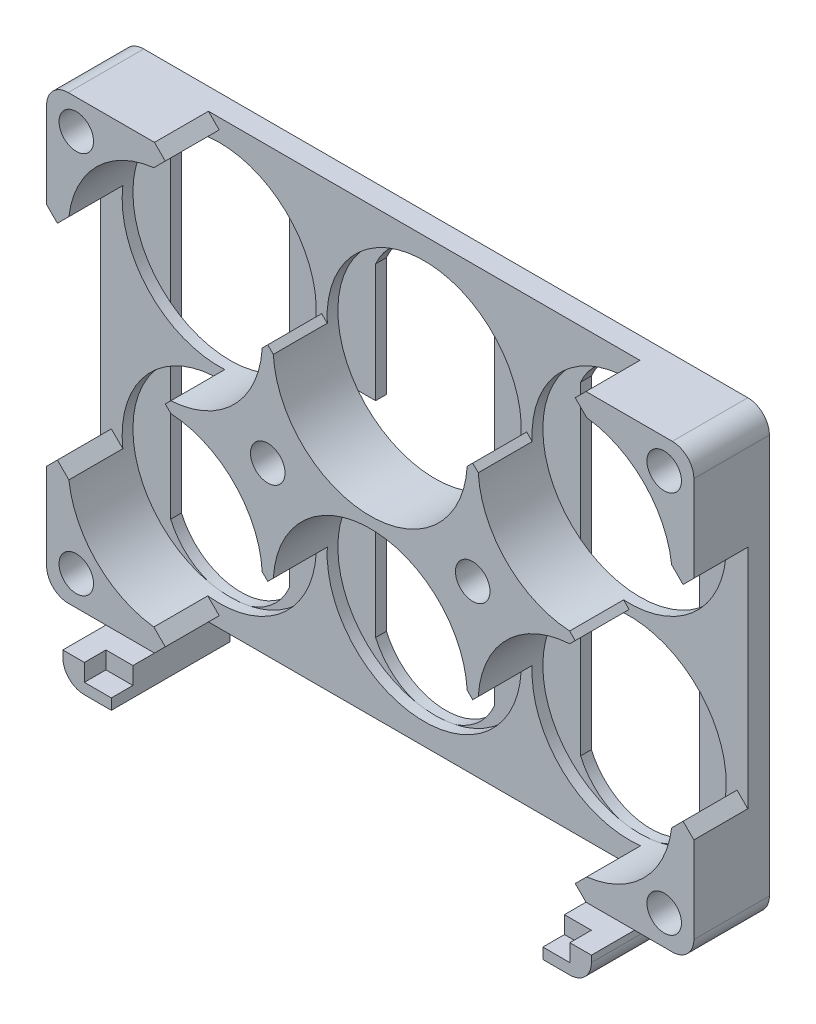
SolidWorks part; units mm, degrees
ref_plane "Płaszczyzna przednia" through (0, 0, 0) normal (0, 0, 1) x (1, 0, 0)
ref_plane "Płaszczyzna górna" through (0, 0, 0) normal (0, 1, 0) x (1, 0, 0)
ref_plane "Płaszczyzna prawa" through (0, 0, 0) normal (1, 0, 0) x (0, 0, -1)
sketch "Sketch1" plane through (0, 0, 0) normal (0, 0, 1) x (1, 0, 0)
  line L1 (0, 0) -> (-60, 0)
  line L2 (0, 0) -> (0, 41)
  line L3 (0, 41) -> (-60, 41)
  line L4 (-60, 0) -> (-60, 41)
  line L5 (0, 0) -> (-60, 41) construction
  line L6 (0, 41) -> (-60, 0) construction
  point P4 (-30, 20.5)
  dimension "D1" = 60
  dimension "D2" = 41
extrude "Boss-Extrude1" add sketch "Sketch1" along normal blind 2
sketch "Sketch2" plane through (0, 0, 2) normal (0, 0, 1) x (1, 0, 0)
  line L0 (-60, 41) -> (-60, 0) construction
  line L1 (-60, 0) -> (0, 0) construction
  circle A0 centre (-49, 11) radius 9
  circle A1 centre (-30, 11) radius 9
  circle A2 centre (-11, 11) radius 9
  circle A3 centre (-30, 30) radius 9
  circle A4 centre (-11, 30) radius 9
  circle A5 centre (-49, 30) radius 9
  dimension "D1" = 18
  dimension "D2" = 11
  dimension "D3" = 11
  dimension "D4" = 3
  dimension "D5" = 2
extrude "Cut-Extrude1" cut sketch "Sketch2" against normal blind 1
sketch "Sketch3" plane through (0, 0, 0) normal (0, 0, -1) x (-1, 0, 0)
  line L0 (60, 41) -> (60, 0) construction
  line L2 (54.5, 35.4979) -> (54.5, 5.4979)
  line L4 (43.5, 35.4979) -> (43.5, 5.4979)
  line L5 (54.5, 35.4979) -> (43.5, 5.4979) construction
  line L6 (54.5, 5.4979) -> (43.5, 35.4979) construction
  line L7 (0, 41) -> (60, 41) construction
  line L8 (60, 0) -> (0, 0) construction
  line L9 (35.5, 35.4979) -> (35.5, 5.4979)
  line L10 (24.5, 35.4979) -> (24.5, 5.4979)
  line L11 (16.5, 35.4979) -> (16.5, 5.4979)
  line L12 (5.5, 35.4979) -> (5.5, 5.4979)
  line L13 (0, 0) -> (0, 41) construction
  arc A0 (43.5, 35.4979) -> (54.5, 35.4979) centre (49, 33.1) cw
  arc A1 (54.5, 5.4979) -> (43.5, 5.4979) centre (49, 7.8958) cw
  arc A2 (35.5, 5.4979) -> (24.5, 5.4979) centre (30, 7.8958) cw
  arc A3 (24.5, 35.4979) -> (35.5, 35.4979) centre (30, 33.1) cw
  arc A4 (16.5, 5.4979) -> (5.5, 5.4979) centre (11, 7.8958) cw
  arc A5 (5.5, 35.4979) -> (16.5, 35.4979) centre (11, 33.1) cw
  point P4 (49, 20.4979)
  dimension "D4" = 6
  dimension "D5" = 6
  dimension "D6" = 7.9
  dimension "D1" = 11
  dimension "D2" = 30
  dimension "D3" = 5.5
  dimension "D7" = 30
  dimension "D8" = 7.8958
  dimension "D10" = 5.5
  dimension "D9" = 3
extrude "Cut-Extrude2" cut sketch "Sketch3" against normal blind 1
sketch "Sketch4" plane through (0, 0, 0) normal (0, 0, -1) x (-1, 0, 0)
  line L0 (43.5, 35.4979) -> (43.5, 5.4979) construction
  line L1 (43.5, 24.5061) -> (35.5, 24.5061)
  line L2 (43.5, 24.5061) -> (43.5, 16.5061)
  line L3 (43.5, 16.5061) -> (35.5, 16.5061)
  line L4 (35.5, 24.5061) -> (35.5, 16.5061)
  line L5 (43.5, 24.5061) -> (35.5, 16.5061) construction
  line L6 (43.5, 16.5061) -> (35.5, 24.5061) construction
  line L7 (35.5, 5.4979) -> (35.5, 35.4979) construction
  point P4 (39.5, 20.5061)
  dimension "D1" = 8
  dimension "D2" = 1.63
extrude "Cut-Extrude3" cut sketch "Sketch4" against normal blind 1
sketch "Sketch5" plane through (0, 0, 2) normal (0, 0, 1) x (1, 0, 0)
  line L0 (-49, 20) -> (-49, 21)
  line L1 (-40, 30) -> (-39, 30)
  line L2 (-40, 11) -> (-39, 11)
  line L3 (-21, 11) -> (-20, 11)
  line L4 (-11, 20) -> (-11, 21)
  line L5 (-20, 30) -> (-21, 30)
  line L6 (-2, 30) -> (0, 30)
  line L7 (0, 0) -> (0, 41) construction
  line L8 (0, 30) -> (0, 41)
  line L9 (0, 41) -> (-11, 41)
  line L10 (0, 41) -> (-60, 41) construction
  line L11 (-11, 41) -> (-11, 39)
  line L12 (-2, 11) -> (0, 11)
  line L13 (0, 11) -> (0, 0)
  line L14 (0, 0) -> (-11, 0)
  line L15 (-60, 0) -> (0, 0) construction
  line L16 (-11, 0) -> (-11, 2)
  line L17 (-49, 2) -> (-49, 0)
  line L18 (-49, 0) -> (-60, 0)
  line L19 (-60, 0) -> (-60, 11)
  line L20 (-60, 41) -> (-60, 0) construction
  line L21 (-60, 11) -> (-58, 11)
  line L22 (-58, 30) -> (-60, 30)
  line L23 (-60, 30) -> (-60, 41)
  line L24 (-60, 41) -> (-49, 41)
  line L25 (-49, 41) -> (-49, 39)
  arc A0 (-49, 20) -> (-40, 11) centre (-49, 11) cw
  circle A1 centre (-49, 11) radius 9 construction
  arc A2 (-49, 21) -> (-40, 30) centre (-49, 30) ccw
  circle A3 centre (-49, 30) radius 9 construction
  arc A4 (-39, 30) -> (-30, 21) centre (-30, 30) ccw
  circle A5 centre (-30, 30) radius 9 construction
  arc A6 (-30, 20) -> (-39, 11) centre (-30, 11) ccw
  circle A7 centre (-30, 11) radius 9 construction
  arc A8 (-30, 20) -> (-21, 11) centre (-30, 11) cw
  arc A9 (-30, 21) -> (-21, 30) centre (-30, 30) ccw
  arc A10 (-20, 30) -> (-11, 21) centre (-11, 30) ccw
  circle A11 centre (-11, 30) radius 9 construction
  arc A12 (-11, 20) -> (-20, 11) centre (-11, 11) ccw
  circle A13 centre (-11, 11) radius 9 construction
  arc A14 (-11, 2) -> (-2, 11) centre (-11, 11) ccw
  arc A15 (-11, 39) -> (-2, 30) centre (-11, 30) cw
  arc A16 (-58, 30) -> (-49, 39) centre (-49, 30) cw
  arc A17 (-58, 11) -> (-49, 2) centre (-49, 11) ccw
extrude "Boss-Extrude2" add sketch "Sketch5" along normal blind 5
sketch "Sketch6" plane through (0, 0, 7) normal (0, 0, 1) x (1, 0, 0)
  line L0 (-21, 11) -> (-20, 11) construction
  line L1 (-20, 30) -> (-21, 30) construction
  line L2 (-11, 20) -> (-11, 21) construction
  line L3 (-49, 21) -> (-49, 20) construction
  line L4 (-39, 30) -> (-40, 30) construction
  line L5 (-60, 41) -> (-60, 30) construction
  line L6 (-49, 41) -> (-60, 41) construction
  line L7 (-60, 0) -> (-49, 0) construction
  line L8 (-60, 11) -> (-60, 0) construction
  line L9 (0, 0) -> (0, 11) construction
  line L10 (-11, 0) -> (0, 0) construction
  line L11 (0, 30) -> (0, 41) construction
  line L12 (0, 41) -> (-11, 41) construction
  circle A0 centre (-39.5, 20.5) radius 1.6
  circle A1 centre (-20.5, 20.5) radius 1.6
  circle A2 centre (-2.75, 2.75) radius 1.6
  circle A3 centre (-2.75, 38.25) radius 1.6
  circle A4 centre (-57.25, 38.25) radius 1.6
  circle A5 centre (-57.25, 2.75) radius 1.6
  dimension "D1" = 3.2
  dimension "D2" = 3.2
  dimension "D3" = 3.2
  dimension "D4" = 3.2
  dimension "D5" = 3.2
  dimension "D6" = 3.2
  dimension "D7" = 9.5
  dimension "D8" = 9.5
  dimension "D9" = 9.5
  dimension "D10" = 9.5
  dimension "D11" = 9.5
  dimension "D12" = 2.75
  dimension "D13" = 2.75
  dimension "D14" = 2.75
  dimension "D15" = 2.75
  dimension "D16" = 2.75
  dimension "D17" = 2.75
  dimension "D18" = 2.75
  dimension "D19" = 2.75
extrude "Cut-Extrude4" cut sketch "Sketch6" against normal through all
chamfer "Chamfer1" distance 1 angle 45 2 edges at (-37.9, 20.5, 1) (-18.9, 20.5, 0)
chamfer "Chamfer2" distance 0.5 angle 45 12 edges at (-39, 30, 4.5) (-40, 30, 4.5) (-49, 21, 4.5) (-49, 20, 4.5) (-39, 11, 4.5) (-40, 11, 4.5) (-21, 11, 4.5) (-20, 11, 4.5) (-11, 20, 4.5) (-11, 21, 4.5) (-21, 30, 4.5) (-20, 30, 4.5)
chamfer "Chamfer3" distance 1 angle 45 16 edges at (-49, 39, 4.5) (-49, 41, 4.5) (-11, 39, 4.5) (-11, 41, 4.5) (0, 30, 4.5) (-2, 30, 4.5) (-2, 11, 4.5) (0, 11, 4.5) (-11, 2, 4.5) (-11, 0, 4.5) (-49, 0, 4.5) (-49, 2, 4.5) (-58, 11, 4.5) (-60, 11, 4.5) (-58, 30, 4.5) (-60, 30, 4.5)
fillet "Fillet1" radius 2 4 edges at (0, 41, 3.5) (0, 0, 3.5) (-60, 41, 3.5) (-60, 0, 3.5)
sketch "Sketch7" plane through (0, 0, 0) normal (0, -1, 0) x (-1, 0, 0)
  line L1 (5.5, -7) -> (7.5, -7)
  line L2 (5.5, -7) -> (5.5, 0)
  line L3 (5.5, 0) -> (7.5, 0)
  line L4 (7.5, -7) -> (7.5, -2)
  line L5 (5.5, -7) -> (7.5, 0) construction
  line L6 (5.5, 0) -> (7.5, -7) construction
  line L7 (58, 0) -> (2, 0) construction
  line L8 (10, 0) -> (7.5, 0)
  line L9 (10, 0) -> (10, -2)
  line L10 (10, -2) -> (7.5, -2)
  line L12 (10, 0) -> (7.5, -2) construction
  line L13 (10, -2) -> (7.5, 0) construction
  line L14 (58, -7) -> (50, -7) construction
  line L15 (50, 0) -> (52.5, 0)
  line L16 (50, 0) -> (50, -2)
  line L17 (50, -2) -> (52.5, -2)
  line L19 (50, 0) -> (52.5, -2) construction
  line L20 (50, -2) -> (52.5, 0) construction
  line L21 (52.5, 0) -> (54.5, 0)
  line L22 (52.5, -2) -> (52.5, -7)
  line L23 (52.5, -7) -> (54.5, -7)
  line L24 (54.5, 0) -> (54.5, -7)
  line L25 (52.5, 0) -> (54.5, -7) construction
  line L26 (52.5, -7) -> (54.5, 0) construction
  point P4 (7.0088, -3.4692)
  point P10 (8.75, -1)
  point P17 (51.25, -1)
  point P21 (53.5, -3.5)
  dimension "D1" = 0
  dimension "D2" = 0
  dimension "D3" = 2.5
  dimension "D4" = 2
  dimension "D5" = 0
  dimension "D6" = 2.5
  dimension "D7" = 2
  dimension "D8" = 2.5
  dimension "D9" = 2.5
  dimension "D10" = 0
  dimension "D11" = 0
extrude "Boss-Extrude3" add sketch "Sketch7" along normal blind 2.6
sketch "Sketch8" plane through (0, 0, 2) normal (0, 0, 1) x (1, 0, 0)
  line L0 (-10, -2.6) -> (-10, 0) construction
  line L1 (-7.5, -2.6) -> (-10, -2.6)
  line L2 (-7.5, -2.6) -> (-7.5, -1.6)
  line L3 (-7.5, -1.6) -> (-10, -1.6)
  line L4 (-10, -2.6) -> (-10, -1.6)
  line L5 (-7.5, -2.6) -> (-10, -1.6) construction
  line L6 (-7.5, -1.6) -> (-10, -2.6) construction
  line L7 (-52.5, -2.6) -> (-52.5, 0) construction
  line L8 (-50, -2.6) -> (-52.5, -2.6)
  line L9 (-50, -2.6) -> (-50, -1.6)
  line L10 (-50, -1.6) -> (-52.5, -1.6)
  line L11 (-52.5, -2.6) -> (-52.5, -1.6)
  line L12 (-50, -2.6) -> (-52.5, -1.6) construction
  line L13 (-50, -1.6) -> (-52.5, -2.6) construction
  point P4 (-8.75, -2.1)
  point P12 (-51.25, -2.1)
  dimension "D1" = 1
  dimension "D2" = 1
extrude "Boss-Extrude4" add sketch "Sketch8" along normal blind 5
fillet "Fillet2" radius 2 2 edges at (-54.5, -2.6, 3.5) (-5.5, -2.6, 3.5)
sketch "Sketch9" plane through (0, 0, 7) normal (0, 0, 1) x (1, 0, 0)
  line L0 (-5.5, 0) -> (-7.5, 0)
  line L1 (-7.5, 0) -> (-7.5, -1.6)
  line L2 (-7.5, -1.6) -> (-10, -1.6)
  line L3 (-10, -1.6) -> (-10, -2.6)
  line L4 (-10, -2.6) -> (-7.5, -2.6)
  line L5 (-54.5, -0.6) -> (-54.5, 0)
  line L6 (-54.5, 0) -> (-52.5, 0)
  line L7 (-52.5, 0) -> (-52.5, -1.6)
  line L8 (-52.5, -1.6) -> (-50, -1.6)
  line L9 (-50, -1.6) -> (-50, -2.6)
  line L10 (-50, -2.6) -> (-52.5, -2.6)
  arc A0 (-5.5, -0.6) -> (-7.5, -2.6) centre (-7.5, -0.6) cw
  arc A1 (-52.5, -2.6) -> (-54.5, -0.6) centre (-52.5, -0.6) cw
  line M2 (-10, -2.6) -> (-7.5, -2.6)
  arc M3 (-7.5, -2.6) -> (-5.5, -0.6) centre (-7.5, -0.6) ccw
  line M4 (-5.5, -0.6) -> (-5.5, 0)
  line M14 (-7.5, 0) -> (-7.5, -1.6)
  line M15 (-7.5, -1.6) -> (-10, -1.6)
  line M16 (-10, -1.6) -> (-10, -2.6)
extrude "Boss-Extrude5" add sketch "Sketch9" along normal blind 4 contours L0 M4 M14 M15 M16 M2 M3 | A1 L10 L9 L8 L7 L6 L5 region at (-7.3916, -1.4853, 7) region at (-52.6084, -1.4853, 7)
sketch "Sketch10" plane through (0, -1.6, 0) normal (0, 1, 0) x (1, 0, 0)
  line L0 (-7.5, -11) -> (-7.5, -2) construction
  line L1 (-10, -9) -> (-7.5, -9)
  line L2 (-10, -9) -> (-10, -2)
  line L3 (-10, -2) -> (-7.5, -2)
  line L4 (-7.5, -9) -> (-7.5, -2)
  line L5 (-10, -9) -> (-7.5, -2) construction
  line L6 (-10, -2) -> (-7.5, -9) construction
  line L7 (-50, -11) -> (-50, -2) construction
  line L8 (-52.5, -9) -> (-50, -9)
  line L9 (-52.5, -9) -> (-52.5, -2)
  line L10 (-52.5, -2) -> (-50, -2)
  line L11 (-50, -9) -> (-50, -2)
  line L12 (-52.5, -9) -> (-50, -2) construction
  line L13 (-52.5, -2) -> (-50, -9) construction
  line L14 (-7.5, -2) -> (-10, -2) construction
  line L15 (-50, -2) -> (-52.5, -2) construction
  point P4 (-8.75, -5.5)
  point P12 (-51.25, -5.5)
  dimension "D1" = 0
  dimension "D2" = 0
  dimension "D3" = 7
  dimension "D4" = 7
extrude "Boss-Extrude6" add sketch "Sketch10" along normal blind 1.6
